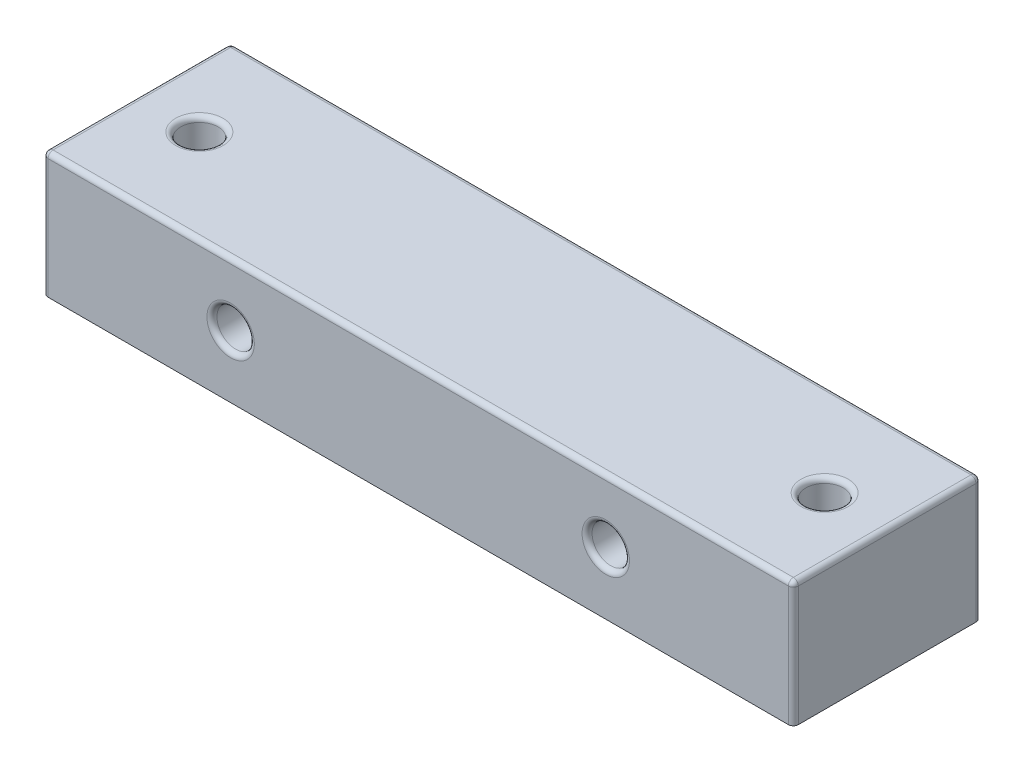
SolidWorks part; units mm, degrees
ref_plane "Front Plane" through (0, 0, 0) normal (0, 0, 1) x (1, 0, 0)
ref_plane "Top Plane" through (0, 0, 0) normal (0, 1, 0) x (1, 0, 0)
ref_plane "Right Plane" through (0, 0, 0) normal (1, 0, 0) x (0, 0, -1)
sketch "Sketch2" plane through (0, 0, 0) normal (0, 0, 1) x (1, 0, 0)
  line L1 (0, 0) -> (76.2, 0)
  line L2 (0, 0) -> (0, 12.7)
  line L3 (0, 12.7) -> (76.2, 12.7)
  line L4 (76.2, 0) -> (76.2, 12.7)
  dimension "D1" = 76.2
  dimension "D2" = 12.7
extrude "Extrude1" add sketch "Sketch2" along normal blind 19.05
hole_wizard "#10-24 Tapped Hole2" positions "3DSketch2" profile "Sketch4" tap size "#10-24" standard "Ansi Inch" end condition up to next
sketch3d "3DSketch2"
  line L0 (0, 12.7, 19.05) -> (0, 0, 19.05) construction
  line L1 (76.2, 0, 19.05) -> (76.2, 12.7, 19.05) construction
  line L2 (0, 0, 19.05) -> (76.2, 0, 19.05) construction
  point P0 (19.05, 6.35, 19.05)
  point P2 (57.15, 6.35, 19.05)
  dimension "D1" = 19.05
  dimension "D2" = 19.05
  dimension "D3" = 6.35
  dimension "D4" = 6.35
sketch "Sketch4" plane through (19.05, 6.35, 19.05) normal (1, 0, 0) x (0, -1, 0)
  line L0 (0, 0) -> (0, 19.05)
  line L1 (0, 19.05) -> (1.8986, 19.05)
  line L2 (1.8986, 19.05) -> (1.8986, 0)
  line L5 (1.8986, 0) -> (0, 0)
  line L11 (0, -6.35) -> (0, 107.95) construction
  dimension "Thread Major Dia." = 3.7973
  dimension "Thru Tap Drill Depth" = 19.05
hole_wizard "#10-24 Tapped Hole3" positions "3DSketch3" profile "Sketch5" tap size "#10-24" standard "Ansi Inch" end condition up to next
sketch3d "3DSketch3"
  line L0 (76.2, 0, 9.525) -> (0, 0, 9.525) construction
  line L1 (76.2, 0, 19.05) -> (76.2, 0, 0) construction
  line L2 (0, 0, 19.05) -> (0, 0, 0) construction
  point P0 (69.85, 0, 9.525)
  point P2 (6.35, 0, 9.525)
  dimension "D1" = 63.5
  dimension "D2" = 6.35
sketch "Sketch5" plane through (69.85, 0, 9.525) normal (1, 0, 0) x (0, 0, -1)
  line L0 (0, 0) -> (0, 12.7)
  line L1 (0, 12.7) -> (1.8986, 12.7)
  line L2 (1.8986, 12.7) -> (1.8986, 0)
  line L5 (1.8986, 0) -> (0, 0)
  line L11 (0, -6.35) -> (0, 107.95) construction
  dimension "Thread Major Dia." = 3.7973
  dimension "Thru Tap Drill Depth" = 12.7
fillet "Fillet1" radius 0.508 14 edges at (76.2, 12.7, 9.525) (38.1, 12.7, 19.05) (0, 12.7, 9.525) (38.1, 12.7, 0) (0, 6.35, 19.05) (0, 6.35, 0) (76.2, 6.35, 19.05) (76.2, 6.35, 0) (17.1514, 6.35, 0) (20.9486, 6.35, 19.05) (55.2514, 6.35, 0) (59.0486, 6.35, 19.05) (6.35, 12.7, 7.6264) (69.85, 12.7, 7.6264)
